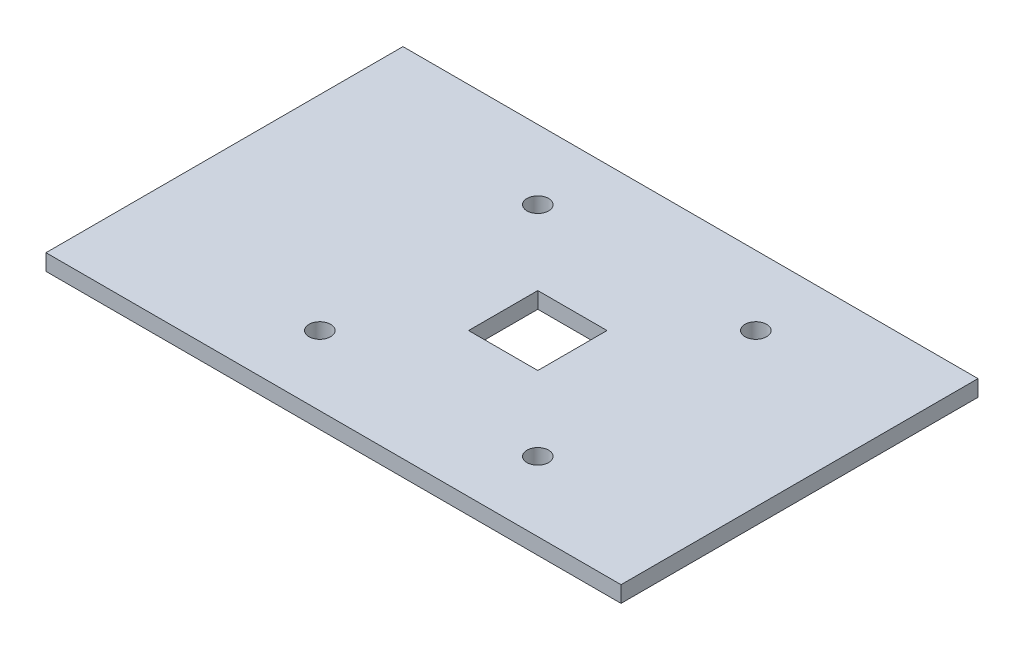
SolidWorks part; units mm, degrees
ref_plane "Front Plane" through (0, 0, 0) normal (0, 0, 1) x (1, 0, 0)
ref_plane "Top Plane" through (0, 0, 0) normal (0, 1, 0) x (1, 0, 0)
ref_plane "Right Plane" through (0, 0, 0) normal (1, 0, 0) x (0, 0, -1)
sketch "Sketch1" plane through (0, 0, 0) normal (0, 1, 0) x (1, 0, 0)
  line L0 (-57.93, -33) -> (48.39, -33)
  line L1 (-57.93, -33) -> (-57.93, 33)
  line L2 (48.39, -33) -> (48.39, 33)
  line L3 (-57.93, 33) -> (48.39, 33)
  line L6 (-6.4, 6.4) -> (6.4, 6.4)
  line L7 (-6.4, 6.4) -> (-6.4, -6.4)
  line L8 (6.4, 6.4) -> (6.4, -6.4)
  line L9 (-6.4, -6.4) -> (6.4, -6.4)
  circle A0 centre (20.1525, -20.1525) radius 2 construction
  circle A1 centre (20.1525, 20.1525) radius 2 construction
  circle A2 centre (-20.1525, -20.1525) radius 2 construction
  circle A3 centre (-20.1525, 20.1525) radius 2 construction
  circle A4 centre (20.1525, -20.1525) radius 2
  circle A5 centre (20.1525, 20.1525) radius 2
  circle A6 centre (-20.1525, -20.1525) radius 2
  circle A7 centre (-20.1525, 20.1525) radius 2
  point P1 (0, 0)
  dimension "D1" = 66
  dimension "D2" = 106.32
  dimension "D3" = 12.8
  dimension "D4" = 6.4
  dimension "D5" = 48.39
  dimension "D6" = 33
  dimension "D7" = 6.4
  dimension "D8" = 12.8
extrude "Boss-Extrude1" add sketch "Sketch1" along normal blind 3
